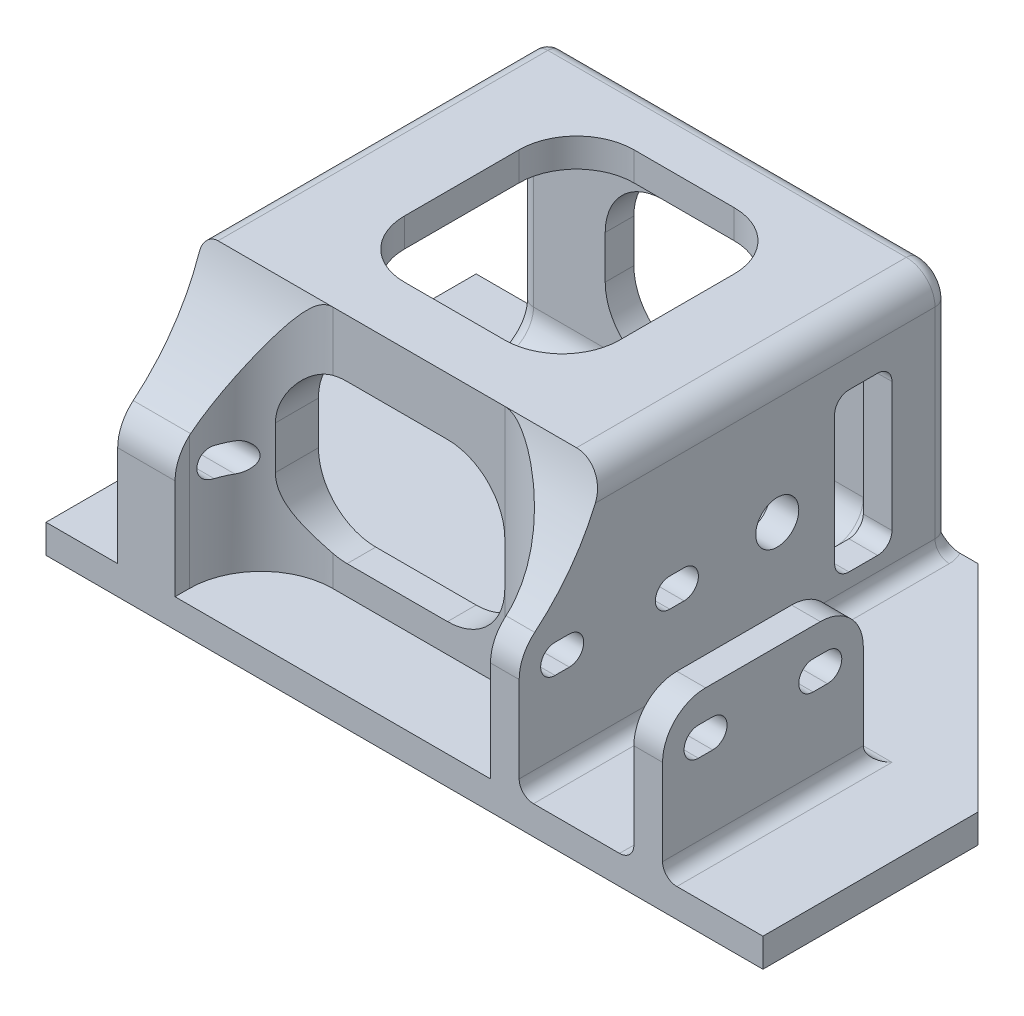
SolidWorks part; units mm, degrees
ref_plane "Front Plane" through (0, 0, 0) normal (0, 0, 1) x (1, 0, 0)
ref_plane "Top Plane" through (0, 0, 0) normal (0, 1, 0) x (1, 0, 0)
ref_plane "Right Plane" through (0, 0, 0) normal (1, 0, 0) x (0, 0, -1)
sketch "Sketch1" plane through (0, 0, 0) normal (0, 1, 0) x (1, 0, 0)
  line L1 (-25, 15) -> (25, 15)
  line L2 (-25, 15) -> (-25, -15)
  line L3 (-25, -15) -> (25, -15)
  line L4 (25, 15) -> (25, -15)
  line L5 (-25, 15) -> (25, -15) construction
  line L6 (-25, -15) -> (25, 15) construction
  point P0 (0, 0)
  dimension "D1" = 50
  dimension "D2" = 30
extrude "Boss-Extrude1" add sketch "Sketch1" along normal blind 2
sketch "Sketch4" plane through (0, 2, 0) normal (0, 1, 0) x (1, 0, 0)
  line L0 (-25, 15) -> (-25, -15) construction
  line L1 (16, -1) -> (18, -1)
  line L2 (16, -1) -> (16, -15)
  line L3 (16, -15) -> (18, -15)
  line L4 (18, -1) -> (18, -15)
  line L5 (16, -1) -> (18, -15) construction
  line L6 (16, -15) -> (18, -1) construction
  line L7 (25, 15) -> (-25, 15) construction
  line L9 (6, -1) -> (8, -1)
  line L10 (6, -1) -> (6, -15)
  line L11 (6, -15) -> (8, -15)
  line L12 (8, -1) -> (8, -15)
  line L13 (6, -1) -> (8, -15) construction
  line L14 (6, -15) -> (8, -1) construction
  line L15 (-20, -9) -> (-16, -9)
  line L16 (-20, -9) -> (-20, -15)
  line L17 (-20, -15) -> (-16, -15)
  line L18 (-16, -9) -> (-16, -15)
  line L19 (-20, -9) -> (-16, -15) construction
  line L20 (-20, -15) -> (-16, -9) construction
  point P0 (17, -8)
  point P7 (17, -1)
  point P10 (7, -8)
  point P15 (-18, -12)
  dimension "D1" = 41
  dimension "D2" = 2
  dimension "D3" = 14
  dimension "D4" = 16
  dimension "D5" = 2
  dimension "D6" = 8
  dimension "D7" = 14
  dimension "D8" = 16
  dimension "D9" = 4
  dimension "D10" = 5
  dimension "D11" = 6
  dimension "D12" = 24
extrude "Boss-Extrude2" add sketch "Sketch4" along normal blind 10
sketch "Sketch7" plane through (0, 2, 0) normal (0, 1, 0) x (1, 0, 0)
  line L0 (25, 15) -> (-25, 15) construction
  line L1 (-20, 15) -> (8, 15)
  line L2 (-20, 15) -> (-20, 13)
  line L3 (-20, 13) -> (8, 13)
  line L4 (8, 15) -> (8, 13)
  line L5 (-20, 15) -> (8, 13) construction
  line L6 (-20, 13) -> (8, 15) construction
  line L7 (-25, 15) -> (-25, -15) construction
  point P0 (-6, 14)
  dimension "D1" = 2
  dimension "D2" = 2
  dimension "D3" = 5
  dimension "D4" = 28
extrude "Boss-Extrude3" add sketch "Sketch7" along normal blind 17
sketch "Sketch8" plane through (0, 2, 0) normal (0, 1, 0) x (1, 0, 0)
  line L1 (8, 13) -> (6, 13)
  line L2 (8, 13) -> (8, -9)
  line L3 (8, -9) -> (6, -9)
  line L4 (6, 13) -> (6, -9)
  dimension "D1" = 2
  dimension "D2" = 22
extrude "Boss-Extrude4" add sketch "Sketch8" along normal blind 17
sketch "Sketch6" plane through (18, 0, 0) normal (1, 0, 0) x (0, 0, -1)
  line L0 (-4.5, 9) -> (-3.5, 9) construction
  line L1 (-4.5, 10) -> (-3.5, 10)
  line L2 (-4.5, 8) -> (-3.5, 8)
  line L4 (-15, 12) -> (-1, 12) construction
  line L5 (-12.5, 9) -> (-11.5, 9) construction
  line L6 (-12.5, 10) -> (-11.5, 10)
  line L7 (-12.5, 8) -> (-11.5, 8)
  line L8 (-15, 12) -> (-15, 2) construction
  arc A0 (-4.5, 10) -> (-4.5, 8) centre (-4.5, 9) ccw
  arc A1 (-3.5, 8) -> (-3.5, 10) centre (-3.5, 9) ccw
  arc A2 (-12.5, 10) -> (-12.5, 8) centre (-12.5, 9) ccw
  arc A3 (-11.5, 8) -> (-11.5, 10) centre (-11.5, 9) ccw
  point P2 (-4, 9)
  point P13 (-12, 9)
  dimension "D1" = 1
  dimension "D2" = 2
  dimension "D3" = 3
  dimension "D4" = 3
  dimension "D5" = 1
  dimension "D6" = 8
  dimension "D7" = 2
extrude "Cut-Extrude2" cut sketch "Sketch6" against normal through all
fillet "Fillet1" radius 3 3 edges at (17, 12, 1) (7, 12, 15) (17, 12, 15)
fillet "Fillet2" radius 3 1 edges at (-18, 12, 15)
sketch "Sketch9" plane through (8, 0, 0) normal (1, 0, 0) x (0, 0, -1)
  line L0 (15, 19) -> (15, 2) construction
  line L1 (-15, 2) -> (15, 2) construction
  circle A0 centre (3, 9.5) radius 1.5
  dimension "D1" = 3
  dimension "D2" = 12
  dimension "D3" = 7.5
extrude "Cut-Extrude3" cut sketch "Sketch9" against normal blind 5
sketch "Sketch10" plane through (0, 2, 0) normal (0, 1, 0) x (1, 0, 0)
  line L0 (6, -9) -> (6, -12) construction
  line L1 (-20, -9) -> (6, -9)
  line L2 (-20, -9) -> (-20, -7)
  line L3 (-20, -7) -> (6, -7)
  line L4 (6, -9) -> (6, -7)
  dimension "D1" = 2
extrude "Boss-Extrude9" add sketch "Sketch10" along normal blind 17
fillet "Fillet14" radius 15 2 edges at (7, 12, 9) (-18, 12, 9)
fillet "Fillet15" radius 2 1 edges at (8, 19, -3)
fillet "Fillet16" radius 5 4 edges at (6, 10.5, 9) (6, 14.771, 10.8588) (-16, 14.771, 10.8588) (-16, 10.5, 9)
sketch "Sketch14" plane through (0, 0, -13) normal (0, 0, 1) x (1, 0, 0)
  line L0 (6, 19) -> (6, 2) construction
  line L1 (-20, 19) -> (6, 19)
  line L2 (-20, 19) -> (-20, 17)
  line L3 (-20, 17) -> (6, 17)
  line L4 (6, 19) -> (6, 17)
  dimension "D1" = 2
extrude "Boss-Extrude11" add sketch "Sketch14" along normal up to next contours L3 L4 L1 L2
fillet "Fillet18" radius 1 4 edges at (8, 9.5, -15) (7.4142, 18.4142, -15) (-7, 19, -15) (-20, 19, -3)
fillet "Fillet19" radius 2 8 edges at (6, 9.5, 7) (6, 2, -3) (6, 17, -3) (-7, 17, 7) (-7, 2, 7) (-7, 2, -13) (-7, 17, -13) (6, 9.5, -13)
fillet "Fillet20" radius 1 9 edges at (-20, 2.5858, 6.4142) (-20, 9.5, 7) (-20, 16.4142, 6.4142) (-20, 16.4142, -12.4142) (-20, 2.5858, -12.4142) (-20, 9.5, -13) (-20, 17, -3) (-19.7071, 18.7071, -14.7071) (-20, 10, -15)
fillet "Fillet21" radius 1 5 edges at (7.7071, 2, -14.7071) (17, 2, 1) (16, 2, 8) (8, 2, 0.5) (18, 2, 8)
sketch "Sketch16" plane through (0, 19, 0) normal (0, 1, 0) x (1, 0, 0)
  line L0 (-19, 14) -> (-19, -9) construction
  line L1 (-14, 11) -> (1, 11)
  line L2 (-14, 11) -> (-14, -5)
  line L3 (-14, -5) -> (1, -5)
  line L4 (1, 11) -> (1, -5)
  line L5 (-14, 11) -> (1, -5) construction
  line L6 (-14, -5) -> (1, 11) construction
  line L7 (6, 14) -> (-19, 14) construction
  point P0 (-6.5, 3)
  dimension "D1" = 16
  dimension "D2" = 15
  dimension "D3" = 5
  dimension "D4" = 3
extrude "Cut-Extrude4" cut sketch "Sketch16" against normal blind 4
fillet "Fillet22" radius 4 4 edges at (1, 18, 5) (-14, 18, 5) (-14, 18, -11) (1, 18, -11)
chamfer "Chamfer2" distance 15 angle 45 1 edges at (25, 1, -15)
sketch "Sketch17" plane through (0, 0, -15) normal (0, 0, -1) x (-1, 0, 0)
  line L0 (19, 2) -> (19, 18) construction
  line L1 (-1, 15) -> (14, 15)
  line L2 (-1, 15) -> (-1, 4)
  line L3 (-1, 4) -> (14, 4)
  line L4 (14, 15) -> (14, 4)
  line L5 (-1, 15) -> (14, 4) construction
  line L6 (-1, 4) -> (14, 15) construction
  line L8 (19, 18) -> (-6, 18) construction
  point P0 (6.5, 9.5)
  dimension "D1" = 15
  dimension "D2" = 5
  dimension "D3" = 3
  dimension "D4" = 11
extrude "Cut-Extrude5" cut sketch "Sketch17" against normal through all contours L2 L3 L4 L1
fillet "Fillet23" radius 4 8 edges at (-14, 4, -14) (-14, 15, -14) (1, 15, -14) (1, 4, -14) (1, 4, 8) (-14, 4, 8.5) (-14, 15, 8.5) (1, 15, 8)
sketch "Sketch18" plane through (8, 0, 0) normal (1, 0, 0) x (0, 0, -1)
  line L0 (14, 3) -> (14, 17) construction
  line L1 (7, 15) -> (11, 15)
  line L2 (7, 15) -> (7, 4)
  line L3 (7, 4) -> (11, 4)
  line L4 (11, 15) -> (11, 4)
  line L5 (7, 15) -> (11, 4) construction
  line L6 (7, 4) -> (11, 15) construction
  line L8 (-15, 3) -> (14, 3) construction
  point P0 (9, 9.5)
  dimension "D1" = 3
  dimension "D2" = 4
  dimension "D3" = 11
  dimension "D4" = 1
extrude "Cut-Extrude6" cut sketch "Sketch18" against normal blind 17
fillet "Fillet24" radius 1 4 edges at (7, 4, -11) (7, 4, -7) (7, 15, -7) (7, 15, -11)
